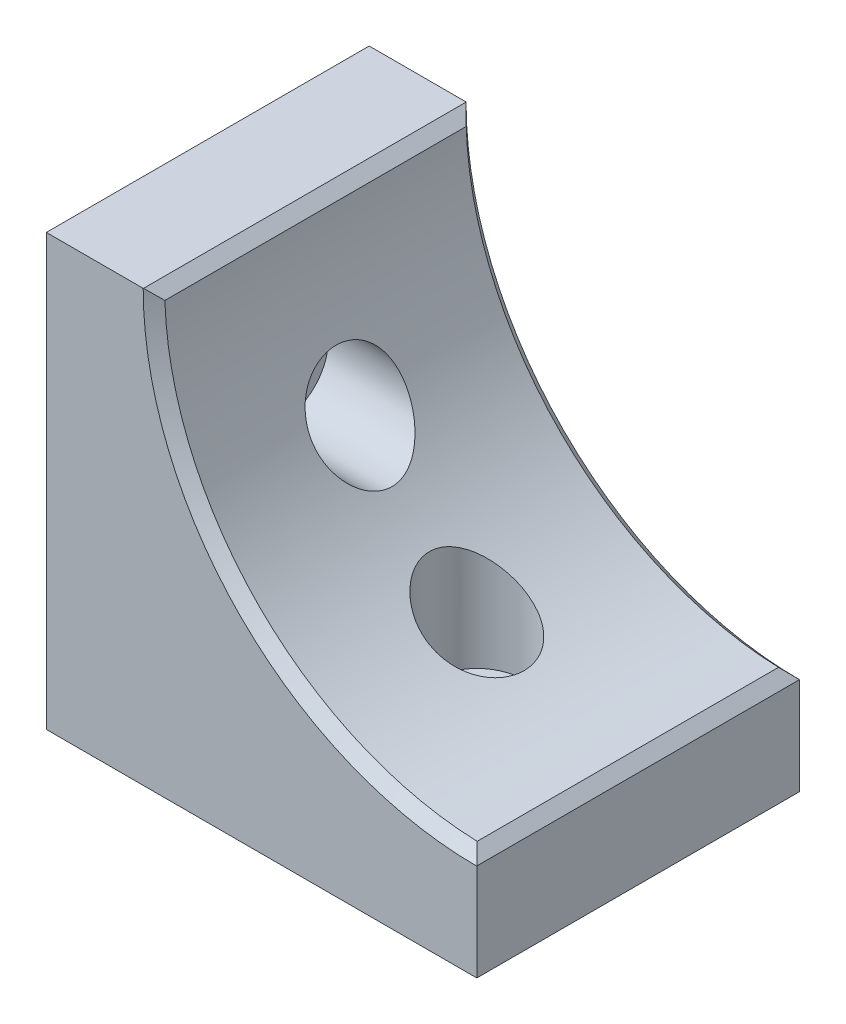
SolidWorks part; units mm, degrees
ref_plane "Front Plane" through (0, 0, 0) normal (0, 0, 1) x (1, 0, 0)
ref_plane "Top Plane" through (0, 0, 0) normal (0, 1, 0) x (1, 0, 0)
ref_plane "Right Plane" through (0, 0, 0) normal (1, 0, 0) x (0, 0, -1)
sketch "Sketch1" plane through (0, 0, 0) normal (0, 1, 0) x (1, 0, 0)
  line L0 (0, 0) -> (0, -38.1)
  line L1 (0, -38.1) -> (50.8, -38.1)
  line L2 (50.8, -38.1) -> (50.8, 0)
  line L3 (50.8, 0) -> (0, 0)
extrude "Boss-Extrude1" add sketch "Sketch1" along normal blind 50.8
sketch "Sketch2" plane through (0, 0, 38.1) normal (0, 0, 1) x (1, 0, 0)
  line L6 (50.8, 50.8) -> (12.7, 50.8)
  line L7 (0, 50.8) -> (50.8, 50.8) construction
  line L8 (12.7, 50.8) -> (12.7, 12.7)
  line L9 (12.7, 12.7) -> (50.8, 12.7)
  line L10 (50.8, 50.8) -> (50.8, 0) construction
  line L11 (50.8, 12.7) -> (50.8, 50.8)
extrude "Cut-Extrude1" cut sketch "Sketch2" against normal up to surface (38.1 mm away) up to face at (25.4, 25.4, 0)
sketch "Sketch3" plane through (0, 12.7, 0) normal (0, 1, 0) x (1, 0, 0)
  line L0 (31.75, 0) -> (31.75, -38.1) construction
  line L1 (50.8, 0) -> (12.7, 0) construction
  line L2 (12.7, -38.1) -> (50.8, -38.1) construction
  circle A0 centre (31.75, -19.05) radius 5.588
  dimension "D1" = 11.176
extrude "Cut-Extrude2" cut sketch "Sketch3" against normal blind 4.064
sketch "Sketch4" plane through (0, 8.636, 0) normal (0, 1, 0) x (1, 0, 0)
  circle A0 centre (31.75, -19.05) radius 3.302
extrude "Cut-Extrude3" cut sketch "Sketch4" against normal up to surface (8.636 mm away) up to face at (25.4, 0, 19.05)
sketch "Sketch5" plane through (12.7, 0, 0) normal (1, 0, 0) x (0, 0, -1)
  line L0 (-38.1, 31.75) -> (0, 31.75) construction
  line L1 (-38.1, 50.8) -> (-38.1, 12.7) construction
  line L2 (0, 12.7) -> (0, 50.8) construction
  circle A0 centre (-19.05, 31.75) radius 5.588
extrude "Cut-Extrude4" cut sketch "Sketch5" against normal blind 4.064
sketch "Sketch6" plane through (8.636, 0, 0) normal (1, 0, 0) x (0, 0, -1)
  circle A0 centre (-19.05, 31.75) radius 3.302
extrude "Cut-Extrude5" cut sketch "Sketch6" against normal up to surface (8.636 mm away) up to face at (0, 25.4, 19.05)
fillet "Fillet1" radius 38.1 1 edges at (12.7, 12.7, 19.05)
chamfer "Chamfer1" distance 1.27 angle 45 4 edges at (50.8, 12.7, 19.05) (23.8592, 23.8592, 0) (12.7, 50.8, 19.05) (23.8592, 23.8592, 38.1)
